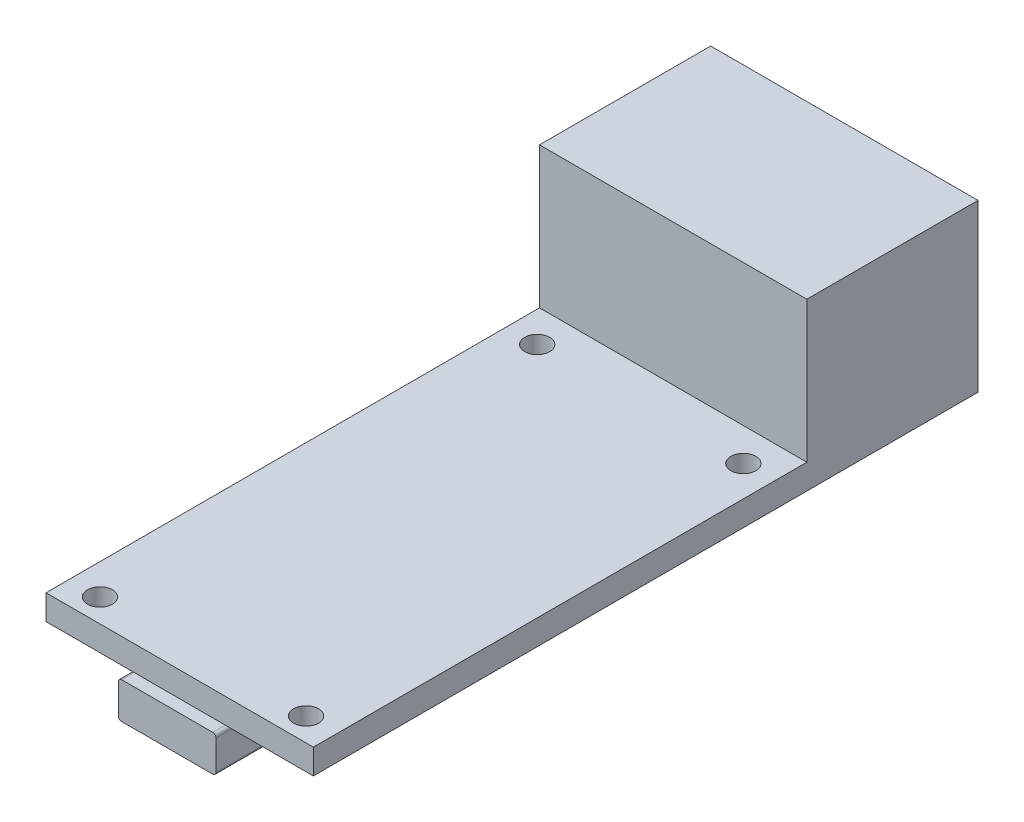
SolidWorks part; units mm, degrees
ref_plane "Front Plane" through (0, 0, 0) normal (0, 0, 1) x (1, 0, 0)
ref_plane "Top Plane" through (0, 0, 0) normal (0, 1, 0) x (1, 0, 0)
ref_plane "Right Plane" through (0, 0, 0) normal (1, 0, 0) x (0, 0, -1)
sketch "Sketch1" plane through (0, 0, 0) normal (0, 1, 0) x (1, 0, 0)
  line L1 (0, 0) -> (21.4, 0)
  line L2 (0, 0) -> (0, 53.2)
  line L3 (0, 53.2) -> (21.4, 53.2)
  line L4 (21.4, 0) -> (21.4, 53.2)
  dimension "D1" = 21.4
  dimension "D2" = 53.2
extrude "Boss-Extrude1" add sketch "Sketch1" along normal blind 2
sketch "Sketch2" plane through (0, 2, 0) normal (0, 1, 0) x (1, 0, 0)
  line L0 (21.4, 0) -> (21.4, 53.2) construction
  line L1 (0, 53.2) -> (21.4, 53.2)
  line L2 (0, 53.2) -> (0, 39.5)
  line L3 (0, 39.5) -> (21.4, 39.5)
  line L4 (21.4, 53.2) -> (21.4, 39.5)
  dimension "D1" = 13.7
extrude "Boss-Extrude2" add sketch "Sketch2" along normal blind 11.3
sketch "Sketch3" plane through (0, 0, -53.2) normal (0, 0, -1) x (-1, 0, 0)
  circle A0 centre (-10.7, 7.65) radius 3.65
extrude "Cut-Extrude1" cut sketch "Sketch3" against normal blind 4 contours A0
sketch "Sketch5" plane through (0, 2, 0) normal (0, 1, 0) x (1, 0, 0)
  line L0 (0, 39.5) -> (0, 0) construction
  line L2 (21.4, 0) -> (21.4, 39.5) construction
  point P0 (2.45, 1.8691)
  point P1 (18.95, 1.8691)
  point P2 (18.95, 36.8691)
  point P3 (2.45, 36.8691)
  point P8 (0, 0)
  dimension "D1" = 16.5
  dimension "D2" = 16.5
  dimension "D3" = 35
  dimension "D4" = 2.45
  dimension "D5" = 2.45
  dimension "D6" = 2.45
hole_wizard "Ø2.0mm Dowel Hole1" positions "Sketch8" profile "Sketch9" hole size "Ø2.0" standard "AS" end condition up to next
sketch "Sketch8" plane through (0, 2, 0) normal (0, 1, 0) x (1, 0, 0)
  point P0 (2.45, 36.8691)
  point P3 (18.95, 36.8691)
  point P6 (18.95, 1.8691)
  point P9 (2.45, 1.8691)
sketch "Sketch9" plane through (2.45, 2, -36.8691) normal (1, 0, 0) x (0, 0, 1)
  line L0 (0, 0) -> (0, 2)
  line L1 (0, 2) -> (1, 2)
  line L2 (1, 2) -> (1, 0)
  line L5 (1, 0) -> (0, 0)
  line L11 (0, -6.35) -> (0, 107.95) construction
  dimension "Thru Hole Dia." = 2
  dimension "Thru Hole Depth" = 2
sketch "Sketch10" plane through (0, 0, 0) normal (0, 0, 1) x (1, 0, 0)
  line L0 (0, 0) -> (21.4, 0) construction
  line L1 (7.05, 0) -> (14.35, 0)
  line L2 (6.8, -0.25) -> (6.8, -2.65)
  line L3 (7.05, -2.9) -> (14.35, -2.9)
  line L4 (14.6, -0.25) -> (14.6, -2.65)
  line L5 (0, 2) -> (0, 0) construction
  arc A0 (14.35, 0) -> (14.6, -0.25) centre (14.35, -0.25) cw
  arc A1 (7.05, 0) -> (6.8, -0.25) centre (7.05, -0.25) ccw
  arc A2 (6.8, -2.65) -> (7.05, -2.9) centre (7.05, -2.65) ccw
  arc A3 (14.35, -2.9) -> (14.6, -2.65) centre (14.35, -2.65) ccw
  point P6 (6.8, -1.45)
  point P11 (14.6, 0)
  point P14 (6.8, 0)
  point P17 (6.8, -2.9)
  point P20 (14.6, -2.9)
  dimension "D4" = 0.25
  dimension "D1" = 7.8
  dimension "D2" = 6.8
  dimension "D3" = 2.9
extrude "Boss-Extrude3" add sketch "Sketch10" along normal blind 1 separate body
extrude "Boss-Extrude4" add sketch "Sketch10<2>" against normal blind 5
sketch "Sketch10<2>" plane through (0, 0, 0) normal (0, 0, 1) x (1, 0, 0) same geometry as "Sketch10"
